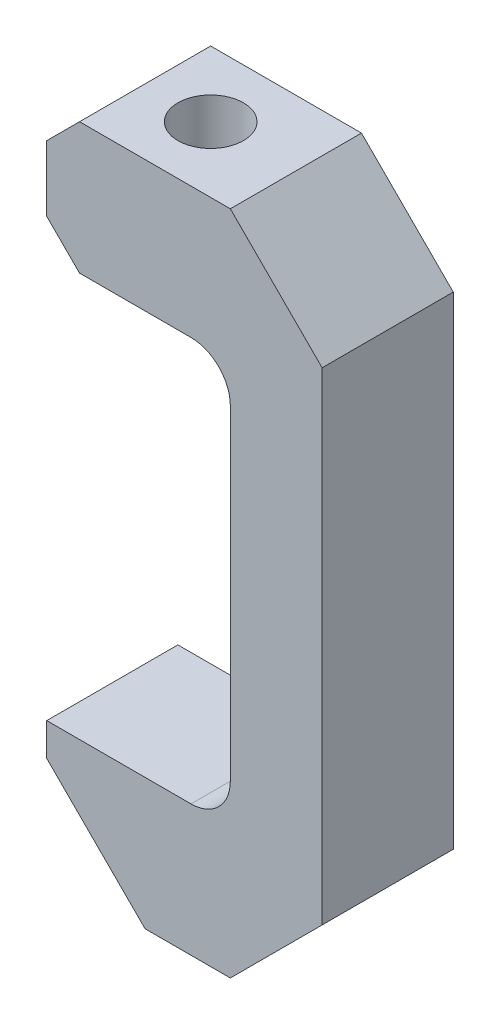
SolidWorks part; units mm, degrees
ref_plane "Front Plane" through (0, 0, 0) normal (0, 0, 1) x (1, 0, 0)
ref_plane "Top Plane" through (0, 0, 0) normal (0, 1, 0) x (1, 0, 0)
ref_plane "Right Plane" through (0, 0, 0) normal (1, 0, 0) x (0, 0, -1)
sketch "Sketch1" plane through (0, 0, 0) normal (0, 0, 1) x (1, 0, 0)
  line L0 (0, 0) -> (0, 73.6)
  line L1 (0, 73.6) -> (-14, 87.6)
  line L2 (-14, 87.6) -> (-37, 87.6)
  line L3 (-42, 82.6) -> (-42, 72.6)
  line L4 (-37, 67.6) -> (-14, 67.6)
  line L5 (-14, 67.6) -> (-14, 6)
  line L7 (-42, 6) -> (-42, 1)
  line L8 (-42, 1) -> (-27, -14)
  line L9 (-27, -14) -> (-14, -14)
  line L10 (-14, -14) -> (0, 0)
  line L11 (-42, 6) -> (-14, 6)
  line L15 (-37, 87.6) -> (-42, 82.6)
  line L16 (-37, 67.6) -> (-42, 72.6)
  dimension "D1" = 101.6
  dimension "D2" = 14
  dimension "D3" = 14
  dimension "D4" = 20
  dimension "D5" = 5
  dimension "D7" = 14
  dimension "D8" = 14
  dimension "D9" = 14
  dimension "D11" = 42
extrude "Boss-Extrude1" add sketch "Sketch1" along normal blind 20 contours L11 | L16 L4 L5 L11 L7 L8 L9 L10 L0 L1 L2 L15 L3 region at (-7.7774, -6.2226, 0)
sketch "Sketch2" plane through (0, 87.6, 0) normal (0, 1, 0) x (1, 0, 0)
  line L0 (-25.5, -5.2303) -> (-25.5, -7.4019) construction
  circle A0 centre (-27, -10) radius 5
extrude "Cut-Extrude4" cut sketch "Sketch2" against normal blind 52
fillet "Fillet3" radius 6 2 edges at (-14, 6, 10) (-14, 67.6, 10)
fillet "Fillet1" radius 6 rebuild error yes
fillet "Fillet2" radius 6 rebuild error yes
